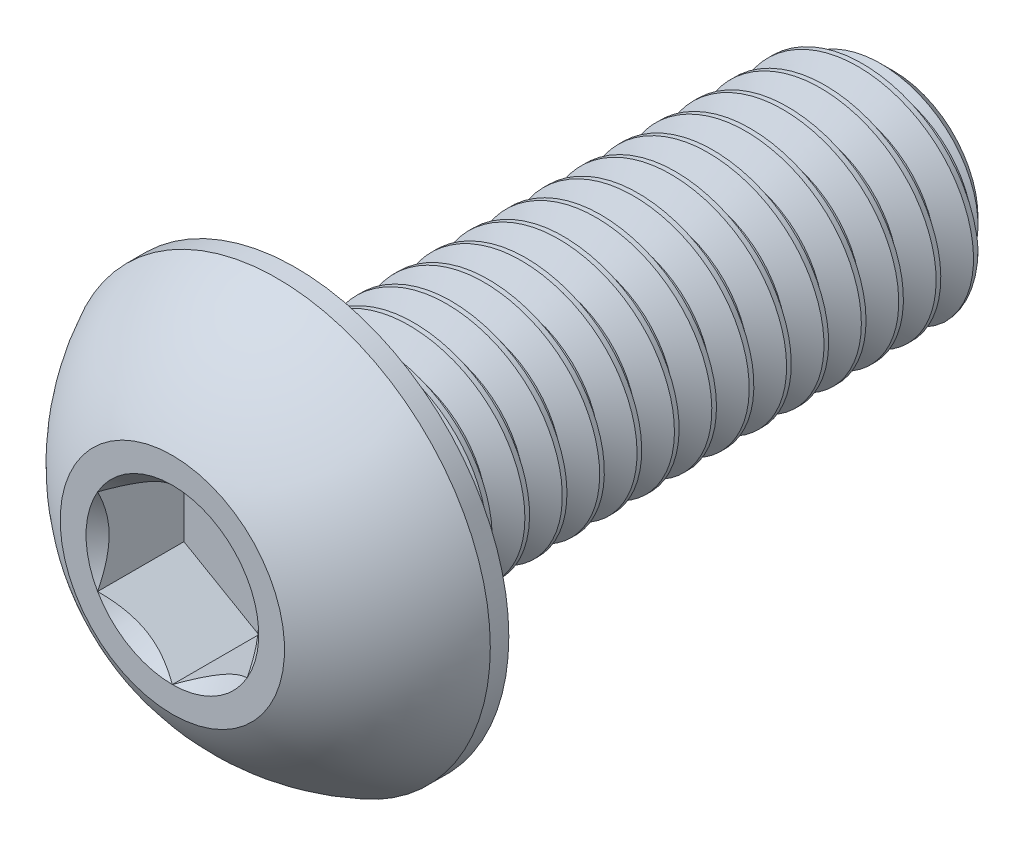
SolidWorks part; units mm, degrees
material "AISI Type 316L stainless steel"
ref_plane "Front" through (0, 0, 0) normal (0, 0, 1) x (1, 0, 0)
ref_plane "Top" through (0, 0, 0) normal (0, 1, 0) x (1, 0, 0)
ref_plane "Right" through (0, 0, 0) normal (1, 0, 0) x (0, 0, -1)
sketch "Sketch1" plane through (0, 0, 0) normal (1, 0, 0) x (0, 0, -1)
  line L2 (1.65, 1.5) -> (9.65, 1.5)
  line L3 (9.65, 1.5) -> (9.65, 0)
  line L4 (9.65, 0) -> (1.65, 0)
  line L6 (1.4025, 2.85) -> (1.65, 2.85) construction
  line L7 (9.65, 1.5) -> (9.65, -1.5) construction
  line L8 (0, 0) -> (1.65, 0) construction
  line L9 (1.65, 2.85) -> (1.65, -2.85) construction
  line L11 (1.65, 1.5) -> (1.65, 0)
  line L13 (0, 1) -> (0, -1) construction
  line L14 (0, 1) -> (0, 1.5) construction
  arc A3 (0, 1.5) -> (1.4025, 2.85) centre (2.7948, 0) cw construction
  dimension "D1" = 0.2475
revolve "Revolve1" add sketch "Sketch1" angle 360 mid plane about L4
sketch "Sketch3" plane through (0, 0, -9.65) normal (0, 0, -1) x (-1, 0, 0)
  circle A0 centre (0, 0) radius 1.5
curve "Helix/Spiral1" pitch 0.5 height 8.5 radius 1.5 centre (0, 0, -9.65) axis (0, 0, 1) start towards (0, 1, 0)
sketch "Sketch2" plane through (0, 0, 0) normal (1, 0, 0) x (0, 0, -1)
  line L0 (9.65, 1.5) -> (10.0875, 1.5)
  line L1 (10.0875, 1.5) -> (9.9, 1.1752)
  line L2 (9.9, 1.1752) -> (9.8375, 1.1752)
  line L3 (9.8375, 1.1752) -> (9.65, 1.5)
  line L4 (9.7438, 1.3376) -> (9.9938, 1.3376) construction
  dimension "D1" = 60
  dimension "D2" = 0.0625
  dimension "D3" = 0.25
chamfer "Chamfer1" distance 0.375 angle 45 1 edges at (0, 1.5, -9.65)
sweep "Cut-Sweep1" cut profiles "Sketch2" path "Helix/Spiral1" align with end faces yes
sketch "Sketch7" plane through (0, 0, 0) normal (1, 0, 0) x (0, 0, -1)
  line L6 (1.4025, 2.85) -> (1.65, 2.85) construction
  line L8 (0, 0) -> (1.65, 0) construction
  line L11 (1.65, 2.85) -> (1.65, -2.85) construction
  line L12 (1.4025, 2.85) -> (1.65, 2.85)
  line L13 (0, 0) -> (1.65, 0)
  line L14 (0, 1) -> (0, -1) construction
  line L15 (1.65, 2.85) -> (1.65, 0)
  line L16 (0, 1.5) -> (0, 0)
  arc A2 (1.4025, 2.85) -> (0, 1.5) centre (2.7948, 0) ccw construction
  arc A3 (1.4025, 2.85) -> (0, 1.5) centre (2.7948, 0) ccw
revolve "Revolve2" add sketch "Sketch7" angle 360 mid plane about L13
sketch "Sketch5" plane through (0, 0, 0) normal (0, 0, 1) x (1, 0, 0)
  line L1 (1, -0.5774) -> (1, 0.5774)
  line L2 (1, 0.5774) -> (0, 1.1547)
  line L3 (0, 1.1547) -> (-1, 0.5774)
  line L4 (-1, 0.5774) -> (-1, -0.5774)
  line L5 (-1, -0.5774) -> (0, -1.1547)
  line L6 (0, -1.1547) -> (1, -0.5774)
  circle A0 centre (0, 0) radius 1 construction
extrude "Cut-Extrude2" cut sketch "Sketch5" against normal blind 1.155
sketch "Sketch6" plane through (0, 0, 0) normal (0, 0, 1) x (1, 0, 0)
  circle A0 centre (0, 0) radius 1.1547
extrude "Cut-Extrude3" cut sketch "Sketch6" against normal blind 1.155 draft 45
sketch "Sketch9" [suppressed] plane through (0, 0, -4.2164) normal (0, 0, 1) x (1, 0, 0)
  circle A2 centre (0, 0) radius 3.9687
extrude "Boss-Extrude2" [suppressed] add sketch "Sketch9" against normal offset from surface (9.525 mm away) 28.575 up to face at (0, 1.125, -9.65)
sketch "Sketch10" plane through (0, 0, 0) normal (1, 0, 0) x (0, 0, -1)
  line L0 (9.65, 1.5) -> (9.65, -1.5) construction
  point P0 (8.9, -1.5)
  dimension "D1" = 0.75
equation "\"D3@Helix/Spiral1\" = \"Lg@Sketch1\" + \"D4@Helix/Spiral1\""
equation "\"D2@Sketch2\" = \"D4@Helix/Spiral1\" * .125"
equation "\"D3@Sketch2\" = \"D4@Helix/Spiral1\" * .5"
equation "\"D1@Chamfer1\" = \"D4@Helix/Spiral1\" * .75"
equation "\"D1@Cut-Extrude2\" = \"Head Ht@Sketch1\" * .7"
equation "\"D1@Sketch1\" = \"Head Ht@Sketch1\" * .15"
equation "\"D1@Sketch10\" = \"D4@Helix/Spiral1\" * 1.5"
equation "\"D1@Cut-Extrude3\" = \"D1@Cut-Extrude2\""
